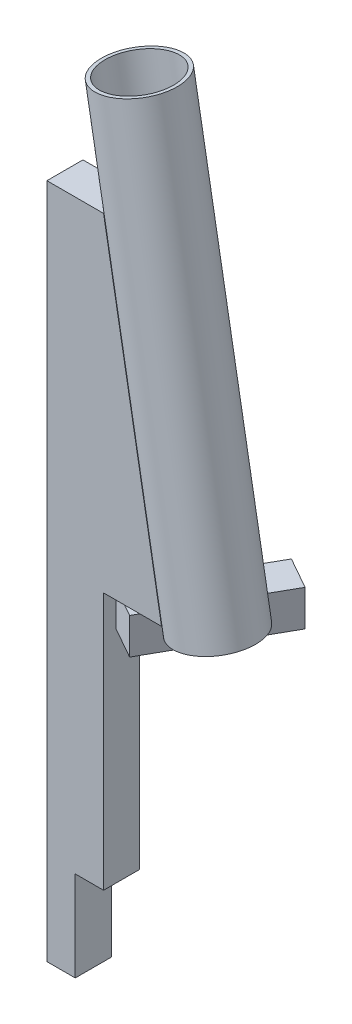
SolidWorks part; units mm, degrees
ref_plane "Front Plane" through (0, 0, 0) normal (0, 0, 1) x (1, 0, 0)
ref_plane "Top Plane" through (0, 0, 0) normal (0, 1, 0) x (1, 0, 0)
ref_plane "Right Plane" through (0, 0, 0) normal (1, 0, 0) x (0, 0, -1)
sketch "Esquisse1" plane through (0, 0, 0) normal (0, 0, 1) x (1, 0, 0)
  line L0 (0, 525.2077) -> (0, 0)
  line L1 (0, 0) -> (22, 0)
  line L2 (22, 0) -> (22, 70)
  line L3 (22, 70) -> (44, 70)
  line L4 (44, 70) -> (44, 270)
  line L5 (44, 270) -> (89, 270)
  line L6 (89, 270) -> (44, 525.2077)
  line L7 (44, 525.2077) -> (0, 525.2077)
  dimension "D1" = 100
  dimension "D2" = 22
  dimension "D3" = 45
  dimension "D4" = 70
  dimension "D5" = 22
  dimension "D6" = 270
extrude "Main Extrusion" add sketch "Esquisse1" along normal mid plane 28
sketch "Esquisse2" plane through (0, 270, 0) normal (0, -1, 0) x (-1, 0, 0)
  line L0 (-76.1897, -6.8856) -> (-51.8103, 6.8856) construction
  line L1 (-69.304, -19.0753) -> (-118.4871, 67.9938)
  line L2 (-69.304, -19.0753) -> (-44.9247, -5.304)
  line L3 (-44.9247, -5.304) -> (-94.1078, 81.765)
  line L4 (-118.4871, 67.9938) -> (-94.1078, 81.765)
  line L5 (-106.2974, 74.8794) -> (-57.1144, -12.1897) construction
  line L9 (-44, -14) -> (-44, 14) construction
  point P8 (-64, 0)
  point P11 (-44, 0)
  point P12 (-94.1078, 81.765)
  dimension "D1" = 28
  dimension "D2" = 100
  dimension "D3" = 86
  dimension "D4" = 20
extrude "Lock Extrusion" add sketch "Esquisse2" along normal blind 28
ref_plane "Plan3" through (-43.489, 246.6386, 0) normal (0.1736, -0.9848, 0) x (0, 0, -1)
sketch "Esquisse3" plane through (-43.489, 246.6386, 0) normal (0.1736, -0.9848, 0) x (0, 0, -1)
  line L2 (-14, 134.5329) -> (14, 134.5329) construction
  line L3 (0, 65.1679) -> (0, -65.1679) construction
  circle A0 centre (0, 164.5329) radius 27
  circle A1 centre (0, 164.5329) radius 30
  dimension "D1" = 60
  dimension "D2" = 54
extrude "Plexiglas" add sketch "Esquisse3" against normal blind 350 separate body
